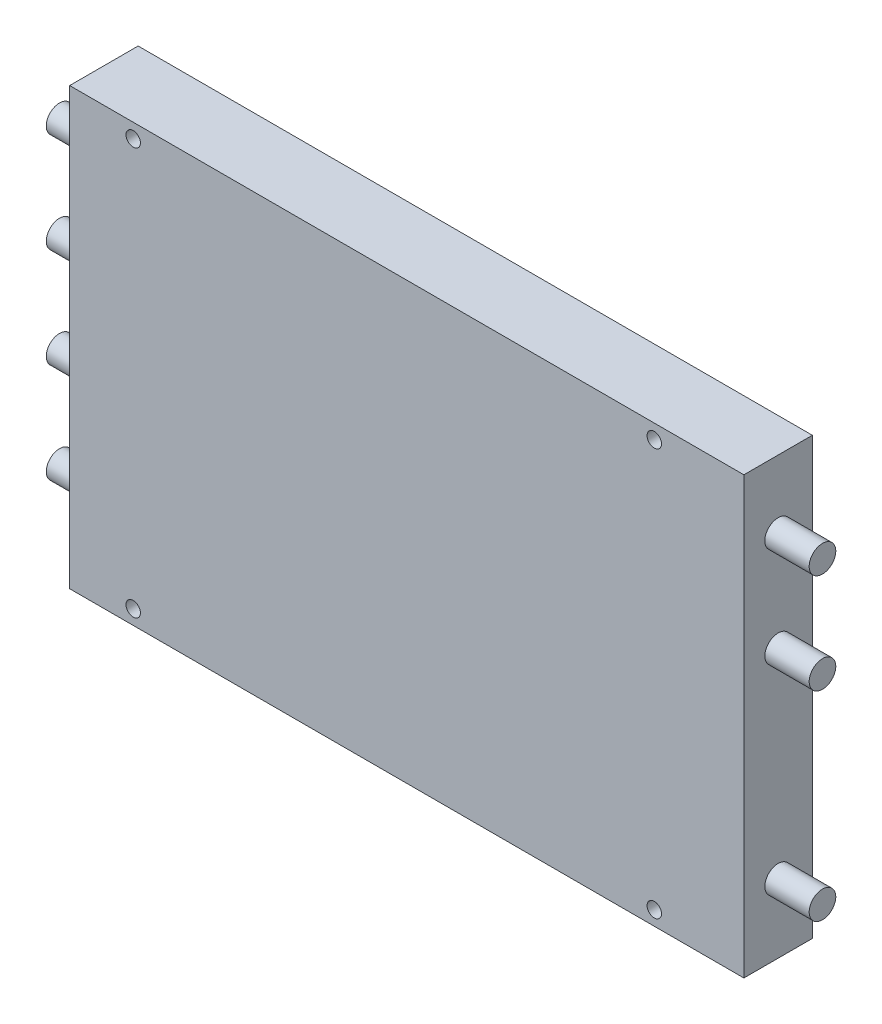
SolidWorks part; units mm, degrees
note: The reader was unsure of these and kept them because the rebuilt part matched: shared geometry of "Sketch2<3>".
ref_plane "Front Plane" through (0, 0, 0) normal (0, 0, 1) x (1, 0, 0)
ref_plane "Top Plane" through (0, 0, 0) normal (0, 1, 0) x (1, 0, 0)
ref_plane "Right Plane" through (0, 0, 0) normal (1, 0, 0) x (0, 0, -1)
sketch "Sketch1" plane through (0, 0, 0) normal (0, 0, 1) x (1, 0, 0)
  line L1 (-77.216, 49.911) -> (77.216, 49.911)
  line L2 (-77.216, 49.911) -> (-77.216, -49.911)
  line L3 (-77.216, -49.911) -> (77.216, -49.911)
  line L4 (77.216, 49.911) -> (77.216, -49.911)
  line L5 (-77.216, 49.911) -> (77.216, -49.911) construction
  line L6 (-77.216, -49.911) -> (77.216, 49.911) construction
  point P0 (0, 0)
  dimension "D1" = 154.432
  dimension "D2" = 99.822
extrude "Boss-Extrude1" add sketch "Sketch1" along normal blind 15.6845
sketch "Sketch2" plane through (-77.216, 0, 0) normal (-1, 0, 0) x (0, 0, 1)
  line L0 (7.8422, 49.911) -> (7.8422, -49.911) construction
  line L1 (15.6845, 49.911) -> (0, 49.911) construction
  line L2 (15.6845, -49.911) -> (0, -49.911) construction
  line L3 (0, 0) -> (15.6845, 0) construction
  line L4 (0, 49.911) -> (0, -49.911) construction
  line L5 (15.6845, 49.911) -> (15.6845, -49.911) construction
  line L9 (15.6845, 49.911) -> (0, 49.911) construction
  circle A1 centre (7.8423, 34.417) radius 3.048
  circle A2 centre (7.8423, 11.557) radius 3.048
  circle A3 centre (7.8423, -11.303) radius 3.048
  circle A4 centre (7.8423, -34.163) radius 3.048
  dimension "D1" = 6.096
  dimension "D2" = 6.096
  dimension "D3" = 6.096
  dimension "D4" = 6.096
  dimension "D5" = 22.86
  dimension "D6" = 22.86
  dimension "D7" = 22.86
  dimension "D8" = 15.494
extrude "Boss-Extrude2" add sketch "Sketch2" along normal blind 10.16 and the other way offset from surface (164.592 mm away) 10.16 contours A1 | A2 | A4 other way up to face at (77.216, 0, 7.8422)
extrude "Boss-Extrude3" add sketch "Sketch2<3>" along normal blind 10.16 contours A3
sketch "Sketch2<3>" plane through (-77.216, 0, 0) normal (-1, 0, 0) x (0, 0, 1) same geometry as "Sketch2"
sketch "Sketch3" plane through (0, 0, 0) normal (0, 0, 1) x (1, 0, 0)
  line L0 (77.216, -49.911) -> (77.216, 49.911) construction
  line L1 (-77.216, -49.911) -> (77.216, -49.911) construction
  line L2 (77.216, 49.911) -> (-77.216, 49.911) construction
  line L3 (-77.216, 49.911) -> (-77.216, -49.911) construction
  circle A0 centre (-62.6618, 46.609) radius 1.651
  circle A1 centre (-62.6618, -46.609) radius 1.651
  circle A2 centre (56.6928, -46.609) radius 1.651
  circle A3 centre (56.6928, 46.609) radius 1.651
  dimension "D1" = 3.302
  dimension "D2" = 3.302
  dimension "D3" = 3.302
  dimension "D4" = 3.302
  dimension "D5" = 20.5232
  dimension "D6" = 3.302
  dimension "D7" = 20.5232
  dimension "D8" = 3.302
  dimension "D9" = 14.5542
  dimension "D10" = 3.302
  dimension "D11" = 3.302
  dimension "D12" = 14.5542
extrude "Cut-Extrude1" cut sketch "Sketch3" along normal through all
equation "\"D6@Sketch2\"=\"D5@Sketch2\""
equation "\"D7@Sketch2\"=\"D5@Sketch2\""
equation "\"D2@Sketch3\"=\"D1@Sketch3\""
equation "\"D3@Sketch3\"=\"D1@Sketch3\""
equation "\"D4@Sketch3\"=\"D1@Sketch3\""
equation "\"D9@Sketch3\"=0.508+0.5*\"D1@Sketch3\""
equation "\"D12@Sketch3\"=\"D9@Sketch3\""
equation "\"D5@Sketch3\"=0.743+0.5*\"D3@Sketch3\""
equation "\"D7@Sketch3\"=\"D5@Sketch3\""
equation "\"D11@Sketch3\"=\"D10@Sketch3\""
equation "\"D6@Sketch3\"=\"D10@Sketch3\""
equation "\"D8@Sketch3\"=\"D10@Sketch3\""
